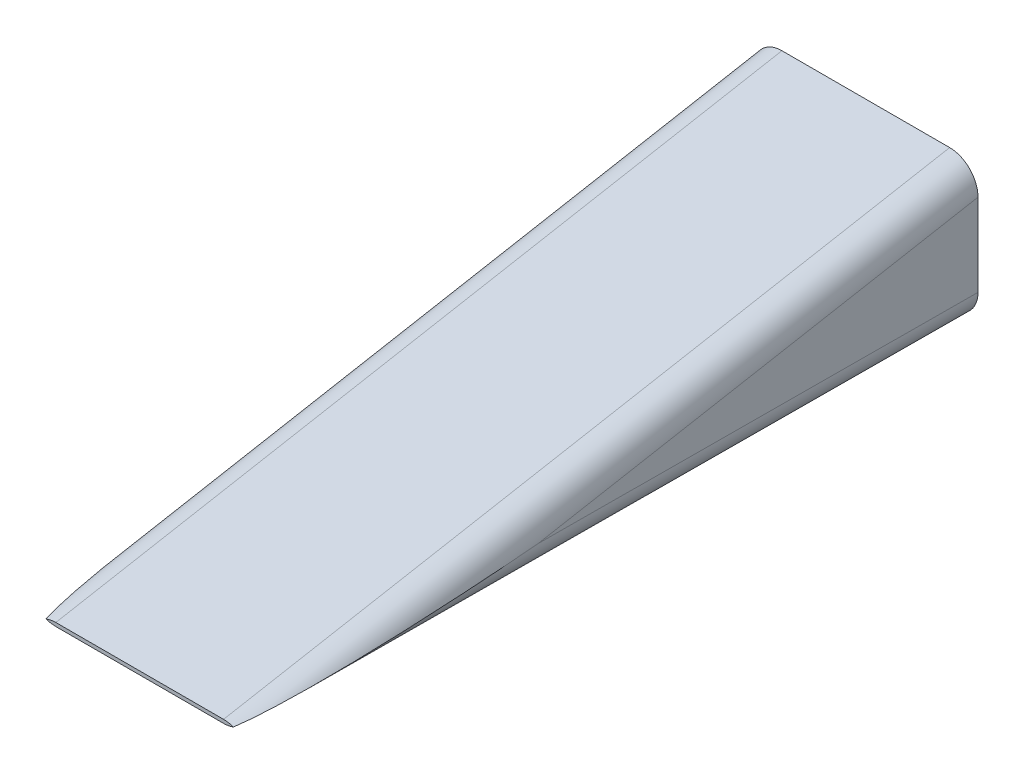
SolidWorks part; units mm, degrees
material "1.3# EPP"
ref_plane "Front Plane" through (0, 0, 0) normal (0, 0, 1) x (1, 0, 0)
ref_plane "Top Plane" through (0, 0, 0) normal (0, 1, 0) x (1, 0, 0)
ref_plane "Right Plane" through (0, 0, 0) normal (1, 0, 0) x (0, 0, -1)
sketch "Sketch1" plane through (0, 0, 0) normal (0, 0, 1) x (1, 0, 0)
  line L0 (16.3068, 8.6995) -> (-16.3068, 8.6995) construction
  line L1 (20.1168, 12.5095) -> (-20.1168, 12.5095)
  line L2 (20.1168, 12.5095) -> (20.1168, -12.5095)
  line L3 (20.1168, -12.5095) -> (-20.1168, -12.5095)
  line L4 (-20.1168, 12.5095) -> (-20.1168, -12.5095)
  line L5 (20.1168, 12.5095) -> (-20.1168, -12.5095) construction
  line L6 (20.1168, -12.5095) -> (-20.1168, 12.5095) construction
  line L7 (-16.3068, 8.6995) -> (-16.3068, -8.6995) construction
  line L8 (16.3068, -8.6995) -> (-16.3068, -8.6995) construction
  line L9 (16.3068, 8.6995) -> (16.3068, -8.6995) construction
  point P0 (0, 0)
  dimension "D1" = 25.019
  dimension "D2" = 40.2336
  dimension "D3" = 3.81
sketch3d "3DSketch1"
  line L1 (0, -6.8008, 130.175) -> (0, 49993.1992, 130.175) construction
  line L2 (0, 0, 130.175) -> (-50000, 0, 130.175) construction
  line L5 (-20.1168, -11.811, 130.175) -> (20.1168, -11.811, 130.175)
  line L6 (-20.1168, -11.811, 130.175) -> (-20.1168, -11.176, 130.175)
  line L7 (-20.1168, -11.176, 130.175) -> (20.1168, -11.176, 130.175)
  line L8 (20.1168, -11.811, 130.175) -> (20.1168, -11.176, 130.175)
  point P1 (0, -11.176, 130.175)
  dimension "D1" = 130.175
  dimension "D2" = 40.2336
  dimension "D3" = 0.635
  dimension "D4" = 11.176
loft "Loft1" add profiles "Sketch1", "3DSketch1" connector at (-20.1168, -12.5095, 0) connector at (-20.1168, -11.811, 130.175)
shell "Shell1" thickness 3.0734 removed face at (0, 0, 0)
fillet "Fillet1" radius 5.08 4 edges
